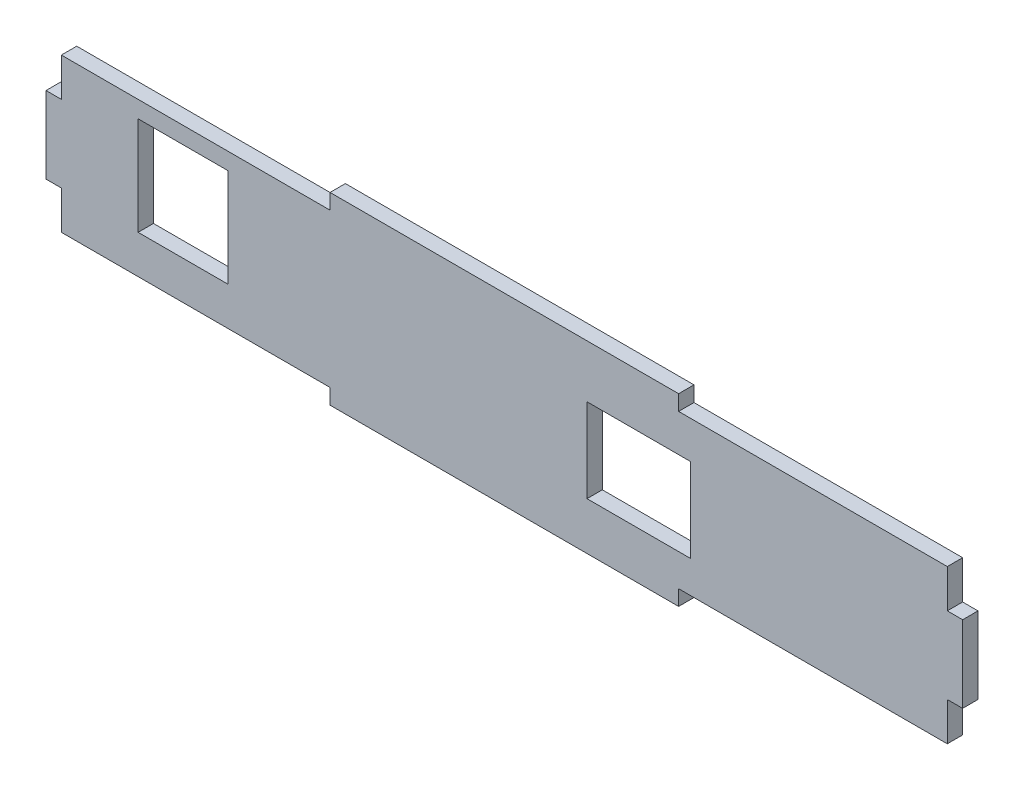
SolidWorks part; units mm, degrees
ref_plane "Front Plane" through (0, 0, 0) normal (0, 0, 1) x (1, 0, 0)
ref_plane "Top Plane" through (0, 0, 0) normal (0, 1, 0) x (1, 0, 0)
ref_plane "Right Plane" through (0, 0, 0) normal (1, 0, 0) x (0, 0, -1)
sketch "Sketch1" plane through (0, 0, 0) normal (0, 0, 1) x (1, 0, 0)
  line L14 (0, 0) -> (35, 0)
  line L15 (35, 0) -> (35, -2.0005)
  line L16 (35, -2.0005) -> (80.41, -2.0005)
  line L17 (80.41, -2.0005) -> (80.41, 0)
  line L18 (80.41, 0) -> (115.41, 0)
  line L19 (0, 0) -> (0, 5)
  line L20 (0, 5) -> (-2, 5)
  line L21 (-2, 5) -> (-2, 15)
  line L22 (-2, 15) -> (0, 15)
  line L23 (0, 15) -> (0, 20)
  line L24 (115.41, 0) -> (115.41, 5)
  line L25 (115.41, 5) -> (117.41, 5)
  line L26 (117.41, 5) -> (117.41, 15)
  line L27 (117.41, 15) -> (115.41, 15)
  line L28 (115.41, 15) -> (115.41, 20)
  line L29 (80.41, 20) -> (80.41, 22)
  line L30 (80.41, 22) -> (35, 22)
  line L31 (35, 22) -> (35, 20)
  line L32 (80.41, 20) -> (115.41, 20)
  line L34 (0, 20) -> (35, 20)
  line L35 (68.4731, 4.1892) -> (81.9297, 4.1892)
  line L36 (10, 5) -> (21.6952, 5)
  line L37 (10, 5) -> (10, 17.8079)
  line L38 (10, 17.8079) -> (21.6952, 17.8079)
  line L39 (21.6952, 5) -> (21.6952, 17.8079)
  line L40 (68.4731, 4.1892) -> (68.4731, 15.1226)
  line L41 (68.4731, 15.1226) -> (81.9297, 15.1226)
  line L42 (81.9297, 4.1892) -> (81.9297, 15.1226)
  point P29 (0, 0)
  dimension "D1" = 10
  dimension "D2" = 115.41
  dimension "D3" = 5
extrude "Boss-Extrude1" add sketch "Sketch1" along normal blind 2
